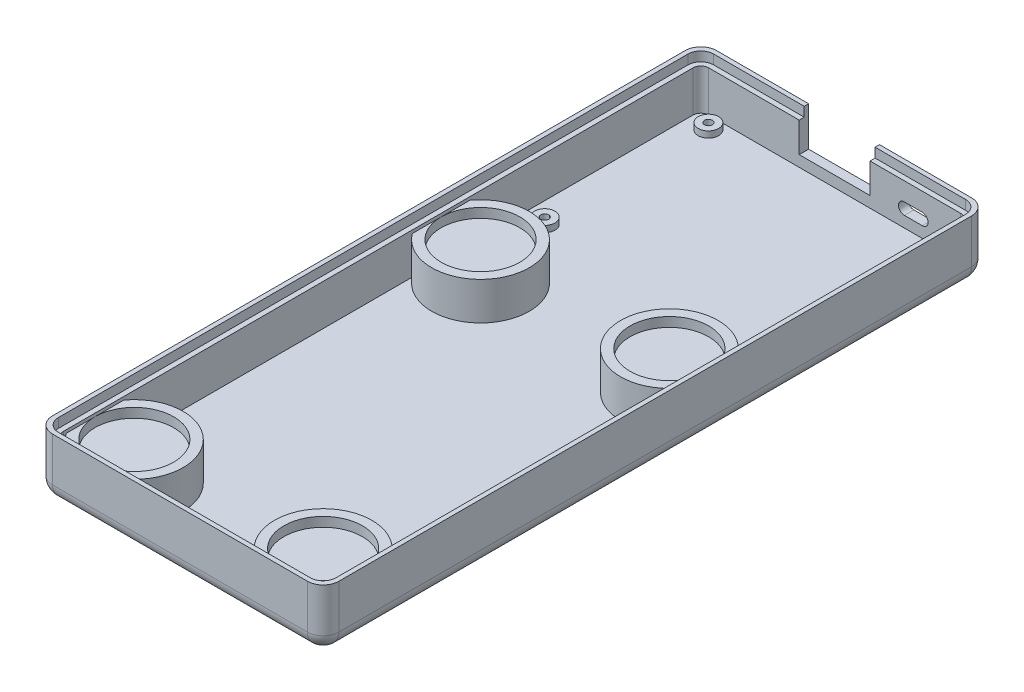
SolidWorks part; units mm, degrees
ref_plane "Front Plane" through (0, 0, 0) normal (0, 0, 1) x (1, 0, 0)
ref_plane "Top Plane" through (0, 0, 0) normal (0, 1, 0) x (1, 0, 0)
ref_plane "Right Plane" through (0, 0, 0) normal (1, 0, 0) x (0, 0, -1)
sketch "Sketch1" plane through (0, 0, 0) normal (0, 1, 0) x (1, 0, 0)
  line L1 (-42.5, 102.5) -> (42.5, 102.5)
  line L2 (-42.5, 102.5) -> (-42.5, -102.5)
  line L3 (-42.5, -102.5) -> (42.5, -102.5)
  line L4 (42.5, 102.5) -> (42.5, -102.5)
  line L5 (-42.5, 102.5) -> (42.5, -102.5) construction
  line L6 (-42.5, -102.5) -> (42.5, 102.5) construction
  point P0 (0, 0)
  dimension "D1" = 85
  dimension "D2" = 205
extrude "Boss-Extrude1" add sketch "Sketch1" along normal blind 3
sketch "Sketch5" plane through (0, 0, 0) normal (0, -1, 0) x (1, 0, 0)
  line L12 (-45.5, 105.5) -> (45.5, 105.5)
  line L13 (-42.5, -102.5) -> (42.5, -102.5)
  line L14 (-42.5, -102.5) -> (-42.5, 102.5)
  line L15 (-42.5, 102.5) -> (42.5, 102.5)
  line L16 (42.5, -102.5) -> (42.5, 102.5)
  line L17 (-42.5, -102.5) -> (42.5, 102.5) construction
  line L18 (-42.5, 102.5) -> (42.5, -102.5) construction
  line L19 (45.5, -105.5) -> (45.5, 105.5)
  line L20 (-45.5, -105.5) -> (45.5, -105.5)
  line L21 (-45.5, -105.5) -> (-45.5, 105.5)
  point P0 (0, 0)
  dimension "D1" = 3
extrude "Boss-Extrude3" add sketch "Sketch5" against normal blind 19
sketch "Sketch3" plane through (0, 3, 0) normal (0, 1, 0) x (1, 0, 0)
  line L0 (0, 102.5) -> (0, 0) construction
  line L2 (-42.5, 102.5) -> (42.5, 102.5) construction
  line L4 (42.5, 102.5) -> (-42.5, 102.5) construction
  circle A0 centre (-36, 98.4) radius 1.25
  circle A1 centre (-36, 98.4) radius 3.25
  circle A2 centre (-36, 46.4) radius 1.25
  circle A3 centre (-36, 46.4) radius 3.25
  circle A4 centre (36, 46.4) radius 3.25
  circle A5 centre (36, 46.4) radius 1.25
  circle A6 centre (36, 98.4) radius 3.25
  circle A7 centre (36, 98.4) radius 1.25
  point P11 (0, 0)
  point P12 (-27.9631, 46.5)
  point P19 (-36, 95.0722)
  point P20 (0, 102.5)
  dimension "D4" = 2.5
  dimension "D5" = 2
  dimension "D6" = 2.5
  dimension "D7" = 2
  dimension "D1" = 36
  dimension "D2" = 52
  dimension "D3" = 4.1
extrude "Boss-Extrude2" add sketch "Sketch3" along normal blind 2
sketch "Sketch2" plane through (0, 3, 0) normal (0, 1, 0) x (1, 0, 0)
  line L0 (0, -102.5) -> (0, 0) construction
  line L5 (-42.5, -102.5) -> (42.5, -102.5) construction
  circle A0 centre (-30, -90) radius 12.5
  circle A1 centre (-30, 20) radius 12.5
  circle A2 centre (30, -90) radius 12.5
  circle A3 centre (30, 20) radius 12.5
  point P9 (-30, -91.0002)
  point P14 (0, -110)
  point P15 (0, -102.5)
  dimension "D5" = 25
  dimension "D6" = 25
  dimension "D1" = 30
  dimension "D2" = 30
  dimension "D3" = 110
extrude "Boss-Extrude4" add sketch "Sketch2" along normal blind 9 separate body
sketch "Sketch4" plane through (0, 3, 0) normal (0, 1, 0) x (1, 0, 0)
  circle A0 centre (36, 98.4) radius 1.25 construction
  circle A1 centre (36, 46.4) radius 1.25 construction
  circle A2 centre (-36, 46.4) radius 1.25 construction
  circle A3 centre (-36, 98.4) radius 1.25 construction
  circle A4 centre (36, 98.4) radius 1.25
  circle A5 centre (36, 46.4) radius 1.25
  circle A6 centre (-36, 46.4) radius 1.25
  circle A7 centre (-36, 98.4) radius 1.25
extrude "Cut-Extrude2" cut sketch "Sketch4" against normal blind 2
sketch "Sketch6" plane through (0, 3, 0) normal (0, 1, 0) x (1, 0, 0)
  circle A0 centre (30, -90) radius 12.5 construction
  circle A2 centre (30, 20) radius 12.5 construction
  circle A4 centre (30, -90) radius 12.5
  circle A5 centre (-30, -90) radius 12.5
  circle A6 centre (30, 20) radius 12.5
  circle A7 centre (-30, 20) radius 12.5
  circle A8 centre (-30, 20) radius 15.5
  circle A9 centre (30, 20) radius 15.5
  circle A10 centre (-30, -90) radius 15.5
  circle A11 centre (30, -90) radius 15.5
  dimension "D1" = 3
extrude "Boss-Extrude5" add sketch "Sketch6" along normal offset from surface (12 mm away) 3 up to face at (30, 12, -32.5) offset beyond the face yes
sketch "Sketch7" plane through (0, 0, -102.5) normal (0, 0, -1) x (-1, 0, 0)
  line L1 (-11.25, 6.5) -> (11.25, 6.5)
  line L2 (-11.25, 6.5) -> (-11.25, 19)
  line L3 (-11.25, 19) -> (11.25, 19)
  line L4 (11.25, 6.5) -> (11.25, 19)
  line L5 (-11.25, 6.5) -> (11.25, 19) construction
  line L6 (-11.25, 19) -> (11.25, 6.5) construction
  line L9 (-22.15, 8.35) -> (-27.85, 8.35) construction
  line L10 (-22.15, 6.5) -> (-27.85, 6.5)
  line L11 (-22.15, 10.2) -> (-27.85, 10.2)
  line L12 (37.25, 5) -> (34.75, 5) construction
  arc A0 (-22.15, 6.5) -> (-22.15, 10.2) centre (-22.15, 8.35) ccw
  arc A1 (-27.85, 10.2) -> (-27.85, 6.5) centre (-27.85, 8.35) ccw
  point P0 (0, 12.75)
  point P5 (-25, 8.35)
  point P15 (11.25, 19)
  dimension "D7" = 5.7
  dimension "D1" = 22.5
  dimension "D2" = 1.5
  dimension "D3" = 12.5
  dimension "D4" = 25
  dimension "D6" = 3.7
extrude "Cut-Extrude3" cut sketch "Sketch7" along normal up to next
fillet "Fillet1" radius 5 4 edges at (45.5, 9.5, 105.5) (-45.5, 9.5, 105.5) (45.5, 9.5, -105.5) (-45.5, 9.5, -105.5)
fillet "Fillet2" radius 5 8 edges at (-44.0355, 0, 104.0355) (0, 0, 105.5) (44.0355, 0, 104.0355) (45.5, 0, 0) (44.0355, 0, -104.0355) (0, 0, -105.5) (-44.0355, 0, -104.0355) (-45.5, 0, 0)
sketch "Sketch8" plane through (42.5, 0, 0) normal (-1, 0, 0) x (0, 0, 1)
  line L0 (-62.5, 8) -> (-62.5, 14) construction
  line L1 (-63.25, 8) -> (-63.25, 14)
  line L2 (-61.75, 8) -> (-61.75, 14)
  line L3 (-62.5, 11) -> (-48.1096, 11) construction
  line L4 (-102.5, 19) -> (-102.5, 3) construction
  line L5 (-29.1652, 3) -> (-102.5, 3) construction
  line L6 (-59.5, 8) -> (-59.5, 14) construction
  line L7 (-60.25, 8) -> (-60.25, 14)
  line L8 (-58.75, 8) -> (-58.75, 14)
  line L9 (-56.5, 8) -> (-56.5, 14) construction
  line L10 (-57.25, 8) -> (-57.25, 14)
  line L11 (-55.75, 8) -> (-55.75, 14)
  line L12 (-62.5, 8) -> (-59.5, 8) construction
  arc A0 (-63.25, 8) -> (-61.75, 8) centre (-62.5, 8) ccw
  arc A1 (-61.75, 14) -> (-63.25, 14) centre (-62.5, 14) ccw
  arc A2 (-60.25, 8) -> (-58.75, 8) centre (-59.5, 8) ccw
  arc A3 (-58.75, 14) -> (-60.25, 14) centre (-59.5, 14) ccw
  arc A4 (-57.25, 8) -> (-55.75, 8) centre (-56.5, 8) ccw
  arc A5 (-55.75, 14) -> (-57.25, 14) centre (-56.5, 14) ccw
  point P2 (-62.5, 11)
  point P17 (-59.5, 11)
  point P24 (-56.5, 11)
  dimension "D4" = 0.75
  dimension "D1" = 40
  dimension "D2" = 8
  dimension "D3" = 6
  dimension "D6" = 3
  dimension "D5" = 3
fillet "Fillet3" radius 2.5 4 edges at (-42.5, 11, -102.5) (42.5, 11, 102.5) (-42.5, 11, 102.5) (42.5, 11, -102.5)
sketch "Sketch10" plane through (0, 19, 0) normal (0, 1, 0) x (1, 0, 0)
  line L0 (40, -102.5) -> (-40, -102.5) construction
  line L1 (42.5, 100) -> (42.5, -100) construction
  line L2 (-42.5, -100) -> (-42.5, 100) construction
  line L4 (40, -102.5) -> (-40, -102.5)
  line L5 (42.5, 100) -> (42.5, -100)
  line L6 (-42.5, -100) -> (-42.5, 100)
  line L7 (-40, 102.5) -> (40, 102.5)
  line L8 (44.1, 100) -> (44.1, -100)
  line L9 (-40, 104.1) -> (40, 104.1)
  line L10 (-44.1, -100) -> (-44.1, 100)
  line L11 (40, -104.1) -> (-40, -104.1)
  arc A0 (40, -102.5) -> (42.5, -100) centre (40, -100) ccw construction
  arc A1 (-42.5, -100) -> (-40, -102.5) centre (-40, -100) ccw construction
  arc A2 (42.5, 100) -> (40, 102.5) centre (40, 100) ccw construction
  arc A3 (-40, 102.5) -> (-42.5, 100) centre (-40, 100) ccw construction
  arc A4 (40, -102.5) -> (42.5, -100) centre (40, -100) ccw
  arc A5 (-42.5, -100) -> (-40, -102.5) centre (-40, -100) ccw
  arc A6 (42.5, 100) -> (40, 102.5) centre (40, 100) ccw
  arc A7 (-40, 102.5) -> (-42.5, 100) centre (-40, 100) ccw
  arc A8 (40, -104.1) -> (44.1, -100) centre (40, -100) ccw
  arc A9 (44.1, 100) -> (40, 104.1) centre (40, 100) ccw
  arc A10 (-40, 104.1) -> (-44.1, 100) centre (-40, 100) ccw
  arc A11 (-44.1, -100) -> (-40, -104.1) centre (-40, -100) ccw
  dimension "D1" = 1.6
extrude "Cut-Extrude5" cut sketch "Sketch10" against normal blind 3
